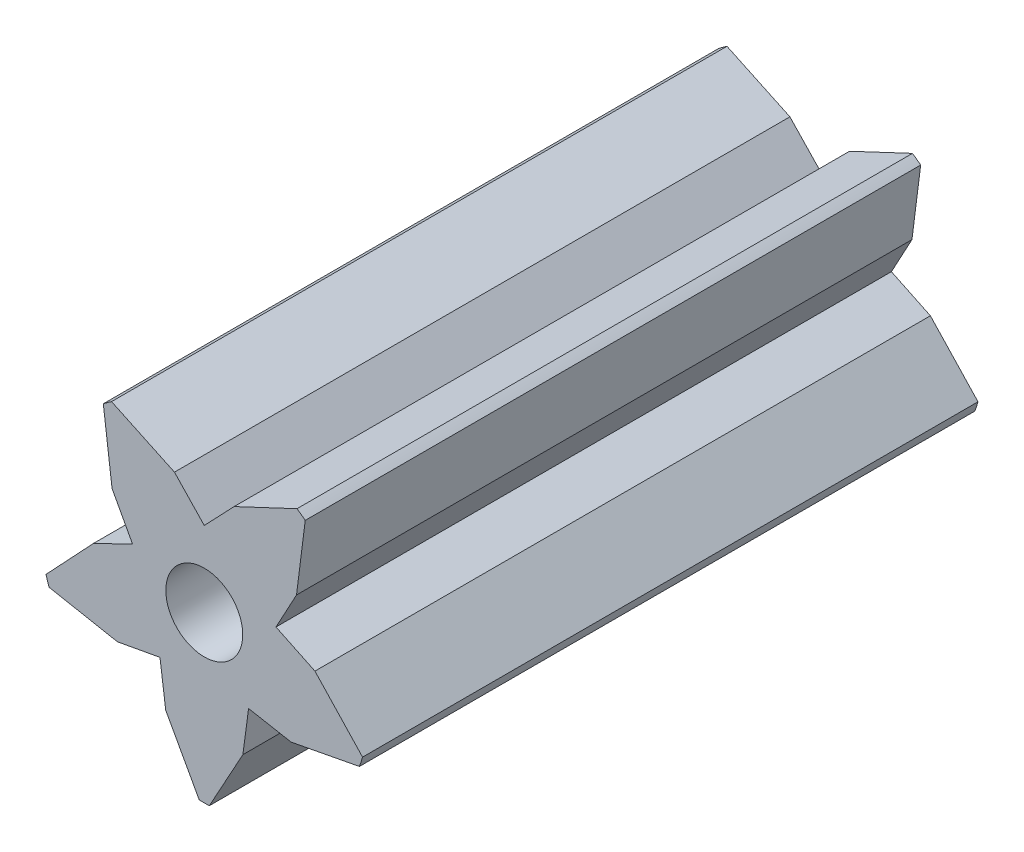
SolidWorks part; units mm, degrees
ref_plane "Front Plane" through (0, 0, 0) normal (0, 0, 1) x (1, 0, 0)
ref_plane "Top Plane" through (0, 0, 0) normal (0, 1, 0) x (1, 0, 0)
ref_plane "Right Plane" through (0, 0, 0) normal (1, 0, 0) x (0, 0, -1)
sketch "Sketch1" plane through (0, 0, 0) normal (0, 0, 1) x (1, 0, 0)
  line L1 (1.2374, -1.2374) -> (-1.2374, -1.2374) construction
  line L2 (1.2374, -1.2374) -> (1.2374, 1.2374) construction
  line L3 (1.2374, 1.2374) -> (-1.2374, 1.2374) construction
  line L4 (-1.2374, -1.2374) -> (-1.2374, 1.2374) construction
  line L5 (1.2374, -1.2374) -> (-1.2374, 1.2374) construction
  line L6 (1.2374, 1.2374) -> (-1.2374, -1.2374) construction
  circle A0 centre (0, 0) radius 7.5
  circle A1 centre (0, 0) radius 1.75
  dimension "D1" = 15
  dimension "D2" = 3.5
extrude "Boss-Extrude1" add sketch "Sketch1" along normal blind 28
sketch "Sketch2" plane through (0, 0, 0) normal (0, 0, 1) x (1, 0, 0)
  line L0 (0, 0) -> (0, 10.088) construction
  line L1 (0, 3.4293) -> (-1.3565, 4.8529)
  line L2 (-1.3565, 4.8529) -> (-4.2191, 6.2007)
  line L3 (-4.2191, 6.2007) -> (0, 11.2516)
  line L4 (4.2191, 6.2007) -> (0, 11.2516)
  line L5 (1.3565, 4.8529) -> (4.2191, 6.2007)
  line L6 (0, 3.4293) -> (1.3565, 4.8529)
  circle A14 centre (0, 0) radius 7.5 construction
  point P16 (0, 7.5)
extrude "Cut-Extrude1" cut sketch "Sketch2" along normal through all
pattern_circular "CirPattern1" count 5 over 360 about axis through (0, 0, 28) along (0, 0, -1) of "Cut-Extrude1" reverse direction yes
sketch "Sketch3" plane through (0, 0, 0) normal (0, 0, 1) x (1, 0, 0)
  circle A0 centre (0, 0) radius 7.5
  dimension "D1" = 15
